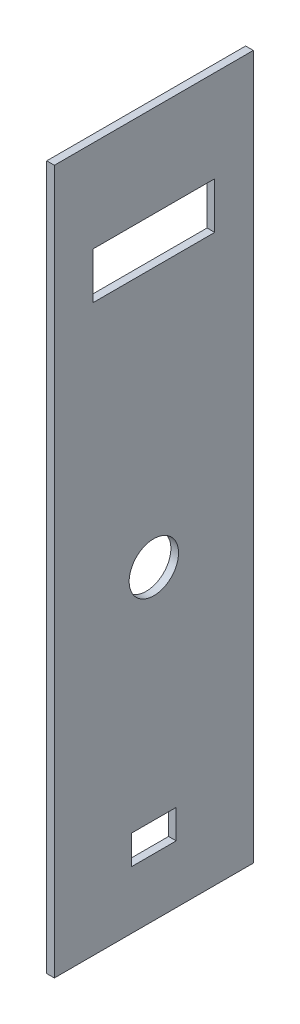
SolidWorks part; units mm, degrees
ref_plane "Front Plane" through (0, 0, 0) normal (0, 0, 1) x (1, 0, 0)
ref_plane "Top Plane" through (0, 0, 0) normal (0, 1, 0) x (1, 0, 0)
ref_plane "Right Plane" through (0, 0, 0) normal (1, 0, 0) x (0, 0, -1)
sketch "Sketch1" plane through (0, 0, 0) normal (1, 0, 0) x (0, 0, -1)
  line L1 (0, 0) -> (82.55, 0)
  line L2 (0, 0) -> (0, 292.1)
  line L3 (0, 292.1) -> (82.55, 292.1)
  line L4 (82.55, 0) -> (82.55, 292.1)
  dimension "D1" = 82.55
  dimension "D2" = 292.1
extrude "Boss-Extrude1" add sketch "Sketch1" along normal blind 3.175 contours L3 L4 L1 L2
sketch "Sketch2" plane through (0, 0, 0) normal (-1, 0, 0) x (0, 0, 1)
  line L0 (0, 292.1) -> (-82.55, 292.1) construction
  line L1 (-66.548, 234.696) -> (-16.002, 234.696)
  line L2 (-66.548, 234.696) -> (-66.548, 254)
  line L3 (-66.548, 254) -> (-16.002, 254)
  line L4 (-16.002, 234.696) -> (-16.002, 254)
  line L5 (0, 292.1) -> (-82.55, 292.1) construction
  point P8 (-41.275, 292.1)
  point P9 (-41.275, 254)
  dimension "D1" = 50.546
  dimension "D2" = 19.304
  dimension "D3" = 38.1
extrude "Cut-Extrude1" cut sketch "Sketch2" against normal up to next
ref_plane "Plane1" through (0, 0, -41.275) normal (0, 0, -1) x (-1, 0, 0)
sketch "Sketch4" plane through (0, 0, 0) normal (-1, 0, 0) x (0, 0, 1)
  line L0 (-41.275, 1.7463) -> (-41.275, -1.7462) construction
  line L2 (0, 0) -> (-82.55, 0) construction
  circle A0 centre (-41.275, 127) radius 10.25
  dimension "D1" = 20.5
  dimension "D2" = 127
extrude "Cut-Extrude2" cut sketch "Sketch4" against normal up to next
sketch "Sketch5" plane through (0, 0, 0) normal (-1, 0, 0) x (0, 0, 1)
  line L0 (-41.275, 1.7463) -> (-41.275, -1.7462) construction
  line L1 (-50.575, 36.05) -> (-31.975, 36.05)
  line L2 (-50.575, 36.05) -> (-50.575, 24)
  line L3 (-50.575, 24) -> (-31.975, 24)
  line L4 (-31.975, 36.05) -> (-31.975, 24)
  line L5 (0, 0) -> (-82.55, 0) construction
  point P4 (-41.275, 36.05)
  dimension "D1" = 12.05
  dimension "D2" = 18.6
  dimension "D3" = 24
extrude "Cut-Extrude3" cut sketch "Sketch5" against normal up to next
